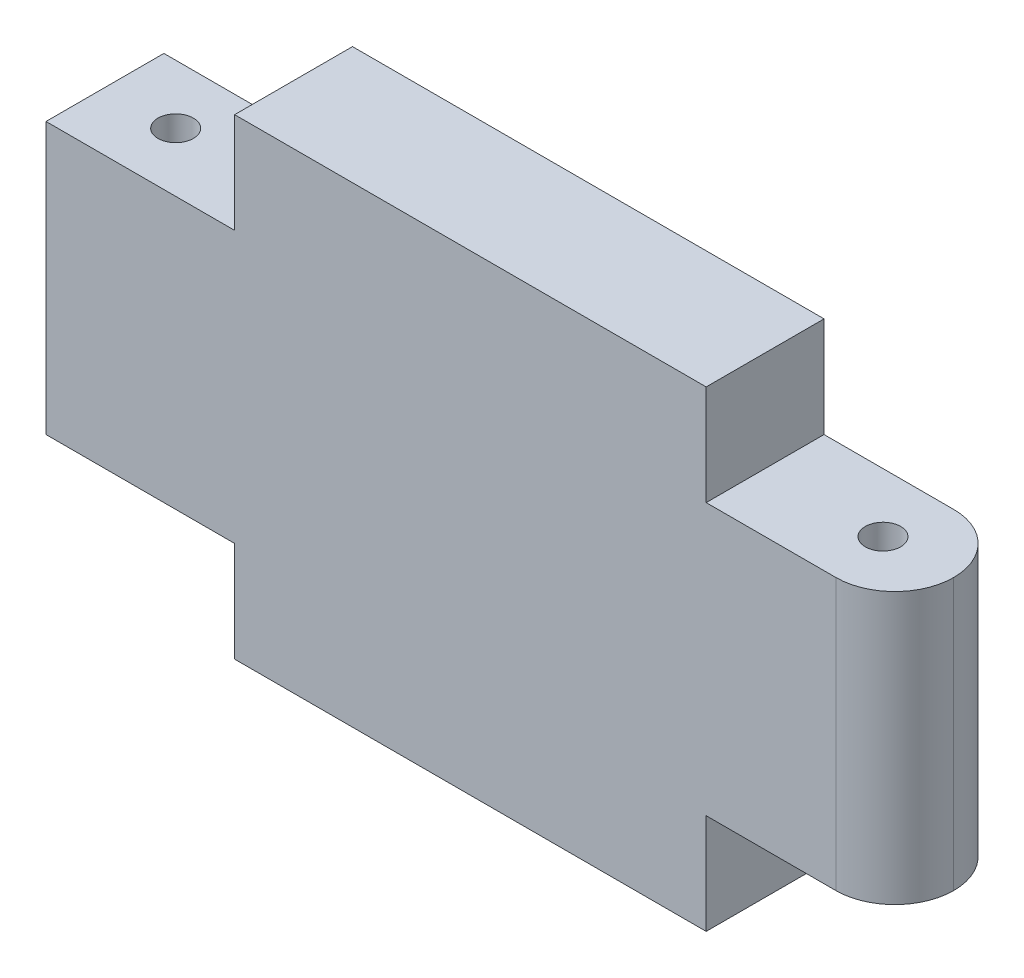
SolidWorks part; units mm, degrees
ref_plane "前视基准面" through (0, 0, 0) normal (0, 0, 1) x (1, 0, 0)
ref_plane "上视基准面" through (0, 0, 0) normal (0, 1, 0) x (1, 0, 0)
ref_plane "右视基准面" through (0, 0, 0) normal (1, 0, 0) x (0, 0, -1)
other "Configuration Table"
sketch "草图1" plane through (0, 0, 0) normal (0, 0, 1) x (1, 0, 0)
  line L1 (-20, 20) -> (20, 20)
  line L2 (-20, 20) -> (-20, -20)
  line L3 (-20, -20) -> (20, -20)
  line L4 (20, 20) -> (20, -20)
  line L5 (-20, 20) -> (20, -20) construction
  line L6 (-20, -20) -> (20, 20) construction
  point P0 (0, 0)
  dimension "D1" = 40
  dimension "D2" = 40
extrude "凸台-拉伸1" add sketch "草图1" along normal blind 10
sketch "草图2" plane through (-20, 0, 0) normal (-1, 0, 0) x (0, 0, 1)
  line L0 (0, 20) -> (0, -20) construction
  line L1 (0, 11.5) -> (10, 11.5)
  line L2 (0, 11.5) -> (0, -11.5)
  line L3 (0, -11.5) -> (10, -11.5)
  line L4 (10, 11.5) -> (10, -11.5)
  line L5 (10, 20) -> (10, -20) construction
  dimension "D1" = 23
  dimension "D2" = 11.5
extrude "凸台-拉伸2" add sketch "草图2" along normal blind 16
sketch "草图3" plane through (0, 11.5, 0) normal (0, 1, 0) x (1, 0, 0)
  line L0 (-36, -10) -> (-36, 0) construction
  line L1 (-36, 0) -> (-20, 0) construction
  circle A0 centre (-30, -5) radius 1.5
  dimension "D1" = 3
  dimension "D2" = 6
  dimension "D3" = 5
extrude "切除-拉伸1" cut sketch "草图3" against normal blind 30
mirror "镜向1" about plane through (0, 0, 0) normal (1, 0, 0) of "切除-拉伸1", "凸台-拉伸2"
fillet "圆角2" radius 5 2 edges at (36, 0, 10) (36, 0, 0)
